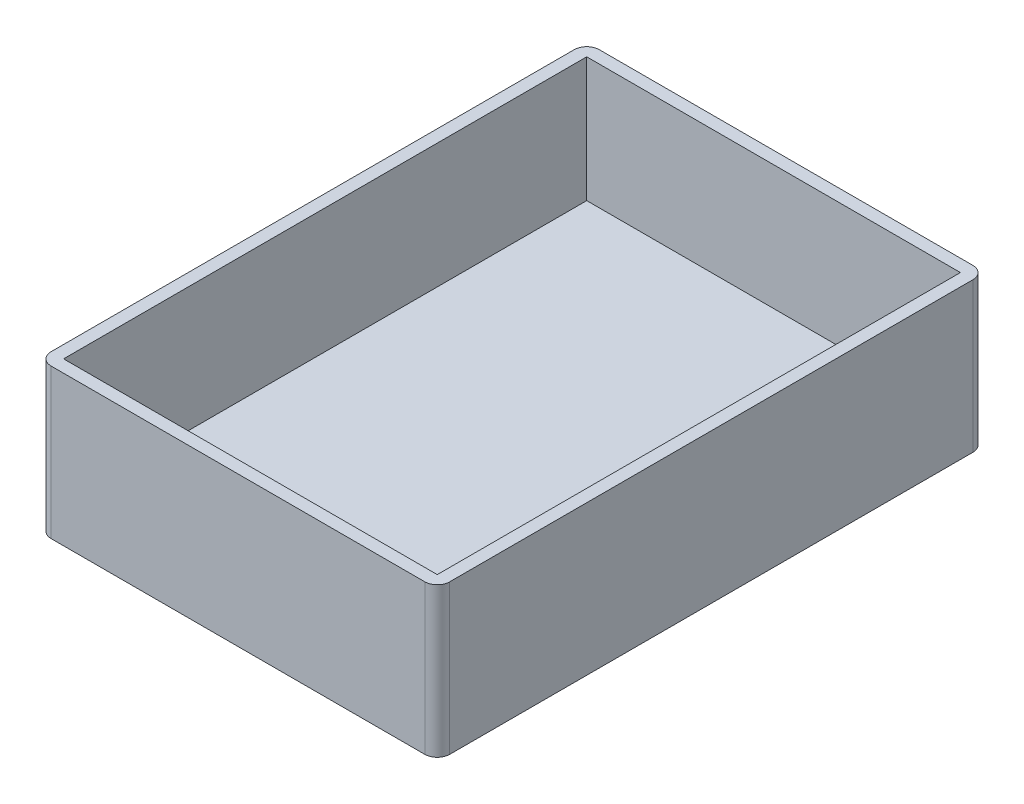
SolidWorks part; units mm, degrees
ref_plane "Front Plane" through (0, 0, 0) normal (0, 0, 1) x (1, 0, 0)
ref_plane "Top Plane" through (0, 0, 0) normal (0, 1, 0) x (1, 0, 0)
ref_plane "Right Plane" through (0, 0, 0) normal (1, 0, 0) x (0, 0, -1)
sketch "Main Body" plane through (0, 0, 0) normal (0, 1, 0) x (1, 0, 0)
  line L0 (-75, 110) -> (75, 110)
  line L1 (-75, -105) -> (75, -105)
  line L2 (-75, -105) -> (-75, 105)
  line L3 (-75, 105) -> (75, 105)
  line L4 (75, -105) -> (75, 105)
  line L5 (-75, -105) -> (75, 105) construction
  line L6 (-75, 105) -> (75, -105) construction
  line L7 (80, -105) -> (80, 105)
  line L8 (-75, -110) -> (75, -110)
  line L9 (-80, -105) -> (-80, 105)
  line L10 (-80, -110) -> (80, -110) construction
  line L11 (-80, -110) -> (-80, 110) construction
  line L12 (80, -110) -> (80, 110) construction
  line L13 (-80, 110) -> (80, 110) construction
  arc A0 (-75, -110) -> (-80, -105) centre (-75, -105) cw
  arc A1 (80, -105) -> (75, -110) centre (75, -105) cw
  arc A2 (75, 110) -> (80, 105) centre (75, 105) cw
  arc A3 (-75, 110) -> (-80, 105) centre (-75, 105) ccw
  point P0 (0, 0)
  dimension "D4" = 5
  dimension "D1" = 75
  dimension "D2" = 210
  dimension "D3" = 5
extrude "Boss-Extrude1" add sketch "Main Body" along normal blind 10 contours L1 L4 L3 L2 | L9 L8 L7 L0 L4 L1 L2 L3 region at (0, 0, -107.2797) region at (0, 0, 0)
extrude "Boss-Extrude3" add sketch "Main Body<4>" along normal blind 50 from surface starting at face at (0, 10, 0)
sketch "Main Body<4>" plane through (0, 0, 0) normal (0, 1, 0) x (1, 0, 0) same geometry as "Main Body"
